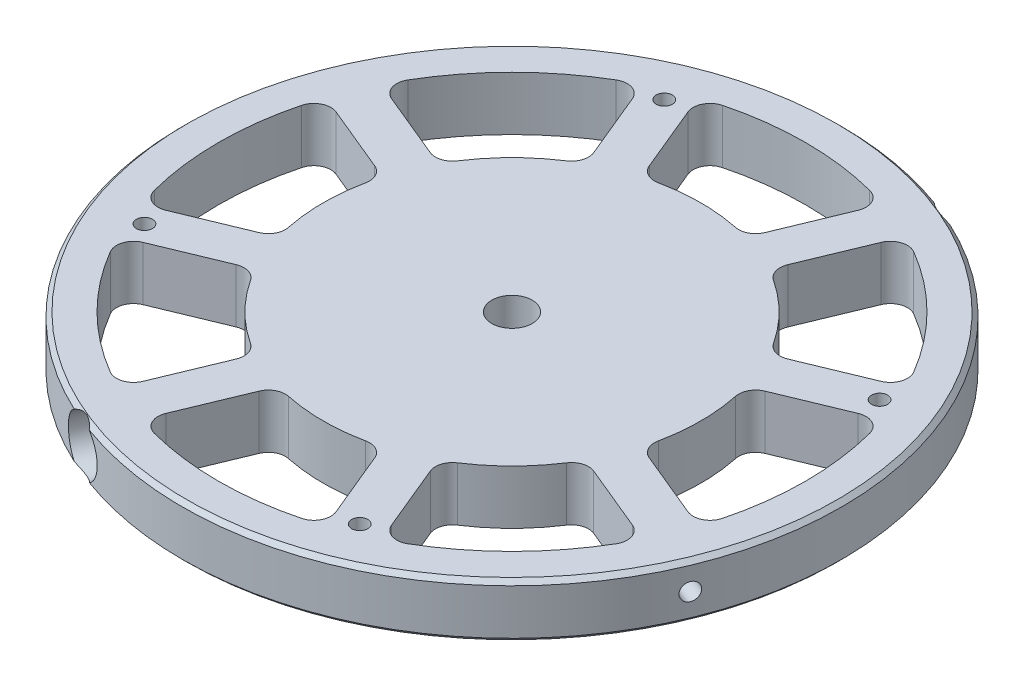
SolidWorks part; units mm, degrees
material "6061-T6 (SS)"
ref_plane "Front Plane" through (0, 0, 0) normal (0, 0, 1) x (1, 0, 0)
ref_plane "Top Plane" through (0, 0, 0) normal (0, 1, 0) x (1, 0, 0)
ref_plane "Right Plane" through (0, 0, 0) normal (1, 0, 0) x (0, 0, -1)
sketch "Sketch2" plane through (0, 0, 0) normal (1, 0, 0) x (0, 0, -1)
  line L0 (0, 0) -> (-77.55, 0)
  line L1 (-77.55, 0) -> (-77.55, 12.7)
  line L2 (-77.55, 12.7) -> (0, 12.7)
  line L5 (0, 12.7) -> (0, 0)
  dimension "D1" = 77.55
  dimension "D2" = 12.7
ref_axis "Axis1" through (0, -0.635, 0) along (0, 1, 0)
revolve "Revolve1" add sketch "Sketch2" angle 360 about axis through (0, -0.635, 0) along (0, 1, 0)
hole_wizard "#10-24 Tapped Hole2" positions "Sketch6" profile "Sketch7" tap size "#10-24" standard "ANSI Inch" end condition through all
sketch "Sketch6" plane through (0, 12.7, 0) normal (0, 1, 0) x (1, 0, 0)
  line L0 (0, 0) -> (-53.438, 129.0108) construction
  line L2 (0, 0) -> (0, 109.0908) construction
  point P0 (-25.3336, 61.1608)
  dimension "D1" = 22.5
  dimension "D2" = 66.2
sketch "Sketch7" plane through (-25.3336, 12.7, -61.1608) normal (1, 0, 0) x (0, 0, 1)
  line L0 (0, 0) -> (0, 12.7)
  line L1 (0, 12.7) -> (1.8986, 12.7)
  line L2 (1.8986, 12.7) -> (1.8986, 0)
  line L5 (1.8986, 0) -> (0, 0)
  line L11 (0, -6.35) -> (0, 107.95) construction
  dimension "Thread Major Dia." = 3.7973
  dimension "Thru Tap Drill Depth" = 12.7
pattern_circular "CirPattern3" count 4 over 360 about axis through (0, -0.635, 0) along (0, 1, 0) of "#10-24 Tapped Hole2"
sketch "Sketch8" plane through (0, 12.7, 0) normal (0, 1, 0) x (1, 0, 0)
  line L4 (0, 0) -> (0, 93.9995) construction
  line L5 (0, 0) -> (113.8372, 0) construction
  line L6 (-12.2829, 42.7192) -> (-21.7355, 65.5398)
  line L7 (12.2829, 42.7192) -> (21.7355, 65.5398)
  line L8 (0, 0) -> (-25.3336, 61.1608) construction
  arc A0 (-12.2829, 42.7192) -> (12.2829, 42.7192) centre (0, 0) cw
  arc A1 (-21.7355, 65.5398) -> (21.7355, 65.5398) centre (0, 0) cw
  circle A2 centre (0, 0) radius 77.55 construction
  dimension "D1" = 44.45
  dimension "D2" = 8.5
  dimension "D3" = 5
extrude "Cut-Extrude1" cut sketch "Sketch8" against normal through all
fillet "Fillet1" radius 4 4 edges at (12.2829, 6.35, -42.7192) (21.7355, 6.35, -65.5398) (-12.2829, 6.35, -42.7192) (-21.7355, 6.35, -65.5398)
pattern_circular "CirPattern4" count 8 over 360 about axis through (0, -0.635, 0) along (0, 1, 0) of "Cut-Extrude1", "Fillet1"
chamfer "Chamfer1" distance 1 angle 45 2 edges at (0, 0, -77.55) (0, 12.7, -77.55)
ref_plane "Plane1" through (0, 0, 0) normal (0.9239, 0, 0.3827) x (0, 1, 0)
hole_wizard "#20 (0.161) Diameter Hole1" positions "Sketch16" profile "Sketch15" hole size "#20" standard "ANSI Inch" end condition through all
sketch "Sketch16" plane through (0, 0, 0) normal (0.9239, 0, 0.3827) x (0, 1, 0)
  point P0 (6.35, 0)
  dimension "D1" = 6.35
sketch "Sketch15" plane through (0, 6.35, 0) normal (0, 1, 0) x (-0.3827, 0, 0.9239)
  line L0 (0, 0) -> (0, 101.324)
  line L1 (0, 101.324) -> (2.0447, 101.324)
  line L2 (2.0447, 101.324) -> (2.0447, 0)
  line L5 (2.0447, 0) -> (0, 0)
  line L11 (0, -6.35) -> (0, 107.95) construction
  dimension "Thru Hole Dia." = 4.0894
  dimension "Thru Hole Depth" = 101.324
ref_plane "Plane2" through (29.6771, 0, -71.6469) normal (0.3827, 0, -0.9239) x (-0.9239, 0, -0.3827)
sketch "Sketch19" plane through (29.6771, 0, -71.6469) normal (0.3827, 0, -0.9239) x (-0.9239, 0, -0.3827)
  line L0 (-76.55, 0) -> (76.55, 0) construction
  line L2 (0, -0.635) -> (0, 13.335) construction
  circle A0 centre (0, 6.35) radius 5.5625 construction
  circle A1 centre (0, 6.35) radius 6.25
  dimension "D1" = 12.5
  dimension "D2" = 6.35
extrude "Cut-Extrude3" cut sketch "Sketch19" against normal blind 5
pattern_circular "CirPattern5" count 2 over 360 about axis through (0, -0.635, 0) along (0, 1, 0) of "Cut-Extrude3"
hole_wizard "#10-24 Tapped Hole1" positions "Sketch20" profile "Sketch21" tap size "#10-24" standard "ANSI Inch"
sketch "Sketch20" plane through (-27.7637, 0, 67.0275) normal (-0.3827, 0, 0.9239) x (0.9239, 0, 0.3827)
  circle A0 centre (0, 6.35) radius 6.25
  circle A1 centre (0, 6.35) radius 6.25 construction
  point P0 (0, 6.35)
sketch "Sketch21" plane through (-27.7637, 6.35, 67.0275) normal (0, 1, 0) x (0.9239, 0, 0.3827)
  line L0 (0, 0) -> (0, 51.9408)
  line L1 (0, 51.9408) -> (1.8986, 50.8)
  line L2 (1.8986, 50.8) -> (1.8986, 0)
  line L5 (1.8986, 0) -> (0, 0)
  line L10 (0, 51.9408) -> (-1.8986, 50.8) construction
  line L11 (0, -6.35) -> (0, 107.95) construction
  dimension "Tap Drill Dia." = 3.7973
  dimension "Tap Drill Depth" = 50.8
  dimension "Drill Angle" = 118
pattern_circular "CirPattern6" count 2 over 360 about axis through (0, -0.635, 0) along (0, 1, 0) of "#10-24 Tapped Hole1"
sketch "Sketch22" plane through (0, 12.7, 0) normal (0, 1, 0) x (1, 0, 0)
  circle A0 centre (0, 0) radius 4.765
  dimension "D1" = 9.53
extrude "Cut-Extrude4" cut sketch "Sketch22" against normal blind 12.8
equation "\"TubeDiameter\" = 6.500in"
equation "\"D1@Sketch2\"=(\"TubeDiameter\"/2)-5mm"
equation "\"D2@Sketch6\"=66.2"
